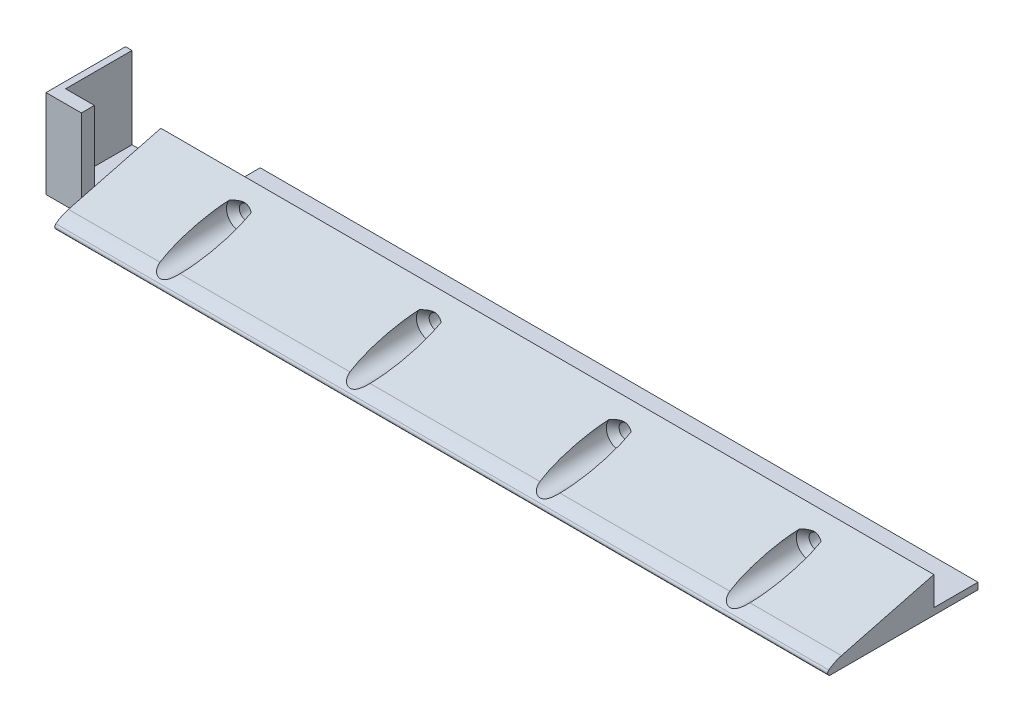
SolidWorks part; units mm, degrees
material "Custom Plastic"
ref_plane "Front Plane" through (0, 0, 0) normal (0, 0, 1) x (1, 0, 0)
ref_plane "Top Plane" through (0, 0, 0) normal (0, 1, 0) x (1, 0, 0)
ref_plane "Right Plane" through (0, 0, 0) normal (1, 0, 0) x (0, 0, -1)
sketch "Sketch1" plane through (0, 0, 0) normal (1, 0, 0) x (0, 0, -1)
  line L0 (0, 6.5) -> (-25, 0)
  line L1 (0, 0) -> (10, 0) construction
  line L2 (0, 0) -> (0, 6.5) construction
  line L3 (0, 6.5) -> (10, 6.5) construction
  line L4 (10, 0) -> (10, 6.5) construction
  line L6 (-25, 0) -> (-25, -1.5)
  line L7 (-25, -1.5) -> (10, -1.5)
  line L8 (10, -1.5) -> (10, 0)
  line L9 (10, 0) -> (0, 0)
  line L10 (0, 0) -> (0, 6.5)
  dimension "D1" = 6.5
  dimension "D2" = 10
  dimension "D3" = 1.5
  dimension "D4" = 25
  dimension "D5" = 8
extrude "Boss-Extrude1" add sketch "Sketch1" along normal blind 175
fillet "Fillet1" radius 8 1 edges at (87.5, 0, 25)
ref_plane "Plane1" through (0, 0, 5) normal (0, 0, -1) x (-1, 0, 0)
sketch "Sketch4" plane through (0, 0, 5) normal (0, 0, -1) x (-1, 0, 0)
  line L0 (0, 0) -> (0, 6.5) construction
  line L1 (-175, 0) -> (-175, 6.5) construction
  line L2 (-175, 0) -> (0, 0) construction
  line L3 (-175, 6.5) -> (0, 6.5) construction
  line L4 (0, 0) -> (0, 6.5) construction
  line L5 (-175, 0) -> (-175, 6.5) construction
  line L6 (-175, 0) -> (0, 0) construction
  line L7 (-175, 6.5) -> (0, 6.5) construction
  line L8 (0, 3.25) -> (-175, 3.25) construction
  circle A0 centre (-23, 3.25) radius 1.5
  circle A1 centre (-66, 3.25) radius 1.5
  circle A2 centre (-109, 3.25) radius 1.5
  circle A3 centre (-152, 3.25) radius 1.5
  point P6 (-23, 3.25)
  point P8 (-66, 3.25)
  point P11 (-109, 3.25)
  point P13 (-152, 3.25)
  dimension "D1" = 3
  dimension "D2" = 23
  dimension "D3" = 4
hole_wizard "CSK for M3 Countersunk Flat Head Screw1" positions "Sketch4" profile "Sketch5" countersink size "M3" standard "ISO" end condition through all
sketch "Sketch5" plane through (152, 3.25, 5) normal (1, 0, 0) x (0, -1, 0)
  line L0 (0, 0) -> (0, 15)
  line L1 (0, 15) -> (1.7, 15)
  line L2 (1.7, 15) -> (1.7, 1.45)
  line L3 (1.7, 1.45) -> (3.15, 0)
  line L5 (3.15, 0) -> (0, 0)
  line L6 (-1.7, 1.45) -> (-3.15, 0) construction
  line L11 (0, -6.35) -> (0, 107.95) construction
  dimension "Thru Hole Dia." = 3.4
  dimension "Thru Hole Depth" = 15
  dimension "Near C'Sink Dia." = 6.3
  dimension "Near C'Sink Angle" = 90
sketch "Sketch7" plane through (0, 0, 5) normal (0, 0, -1) x (-1, 0, 0)
  line L0 (-20.5261, 5.2) -> (-25.4739, 5.2) construction
  line L1 (-149.5261, 5.2) -> (-154.4739, 5.2)
  line L2 (-149.5261, 5.2) -> (-154.4739, 5.2)
  line L3 (-63.5261, 5.2) -> (-68.4739, 5.2) construction
  line L4 (-106.5261, 5.2) -> (-111.4739, 5.2) construction
  line L5 (-20.5261, 5.2) -> (-25.4739, 5.2)
  line L6 (-63.5261, 5.2) -> (-68.4739, 5.2)
  line L7 (-106.5261, 5.2) -> (-111.4739, 5.2)
  arc A0 (-25.4739, 5.2) -> (-20.5261, 5.2) centre (-23, 3.25) ccw construction
  arc A1 (-154.4739, 5.2) -> (-149.5261, 5.2) centre (-152, 3.25) ccw
  arc A2 (-154.4739, 5.2) -> (-149.5261, 5.2) centre (-152, 3.25) ccw
  arc A3 (-68.4739, 5.2) -> (-63.5261, 5.2) centre (-66, 3.25) ccw construction
  arc A4 (-111.4739, 5.2) -> (-106.5261, 5.2) centre (-109, 3.25) ccw construction
  arc A5 (-25.4739, 5.2) -> (-20.5261, 5.2) centre (-23, 3.25) ccw
  arc A6 (-68.4739, 5.2) -> (-63.5261, 5.2) centre (-66, 3.25) ccw
  arc A7 (-111.4739, 5.2) -> (-106.5261, 5.2) centre (-109, 3.25) ccw
  dimension "D1" = 0
extrude "Cut-Extrude2" cut sketch "Sketch7" against normal through all
sketch "Sketch8" plane through (0, 0, 0) normal (0, 1, 0) x (1, 0, 0)
  line L1 (0, 10) -> (12.5, 10)
  line L2 (0, 10) -> (0, 0)
  line L3 (0, 0) -> (12.5, 0)
  line L4 (0, 10) -> (0, 0)
  line L5 (0, 0) -> (175, 0)
  line L6 (175, 0) -> (175, 10)
  line L7 (175, 10) -> (0, 10)
  line L8 (0, 10) -> (0, 0)
  line L9 (0, 0) -> (175, 0)
  line L10 (175, 0) -> (175, 10)
  line L11 (175, 10) -> (0, 10)
  line L12 (12.5, 10) -> (12.5, 0)
  line M5 (0, 10) -> (0, 0)
  line M6 (0, 0) -> (175, 0)
  line M8 (175, 10) -> (0, 10)
  dimension "D2" = 12.5
  dimension "D1" = 0
extrude "Cut-Extrude3" cut sketch "Sketch8" against normal through all contours L12 M8 M5 M6 region at (6.25, 0, -5)
sketch "Sketch10" plane through (0, -1.5, 0) normal (0, -1, 0) x (1, 0, 0)
  line L0 (0, 0) -> (-8, 0)
  line L1 (-8, 0) -> (-8, 18)
  line L2 (-8, 18) -> (0, 18)
  line L6 (12.5, 0) -> (12.5, -10)
  line L7 (12.5, -10) -> (175, -10)
  line L8 (175, -10) -> (175, 25)
  line L9 (175, 25) -> (0, 25)
  line L10 (0, 25) -> (0, 0)
  line L11 (0, 0) -> (12.5, 0)
  line L12 (12.5, 0) -> (12.5, -10)
  line L13 (12.5, -10) -> (175, -10)
  line L14 (175, -10) -> (175, 25)
  line L16 (0, 25) -> (0, 0)
  line L17 (0, 0) -> (12.5, 0)
  line L21 (175, 25) -> (0, 25)
  line M14 (0, 25) -> (0, 0)
  dimension "D2" = 8
  dimension "D3" = 18
  dimension "D1" = 0
extrude "Boss-Extrude2" add sketch "Sketch10" against normal blind 1.5 contours L2 L1 L0 M14 region at (-4, -1.5, 9)
sketch "Sketch11" plane through (0, 0, 0) normal (0, 1, 0) x (1, 0, 0)
  line L0 (-6.52, 0) -> (-6.52, -15.05)
  line L1 (-6.52, -15.05) -> (0, -15.05)
  line L4 (-8, -18) -> (0, -18)
  line L5 (0, -18) -> (0, 0)
  line L6 (0, 0) -> (-8, 0)
  line L7 (-8, 0) -> (-8, -18)
  line L8 (-8, -18) -> (0, -18)
  line L9 (0, -18) -> (0, 0)
  line L10 (0, 0) -> (-8, 0)
  line L11 (-8, 0) -> (-8, -18)
  line M7 (-8, -18) -> (0, -18)
  line M8 (0, -18) -> (0, 0)
  line M9 (0, 0) -> (-8, 0)
  line M10 (-8, 0) -> (-8, -18)
  dimension "D2" = 1.48
  dimension "D3" = 2.95
  dimension "D1" = 0
extrude "Boss-Extrude3" add sketch "Sketch11" along normal blind 18.5 contours L1 L0 M9 M10 M7 M8 region at (-6.717, 0, 7.525)
fillet "Fillet2" radius 0.65 1 edges at (87.5, -1.5, 25)
